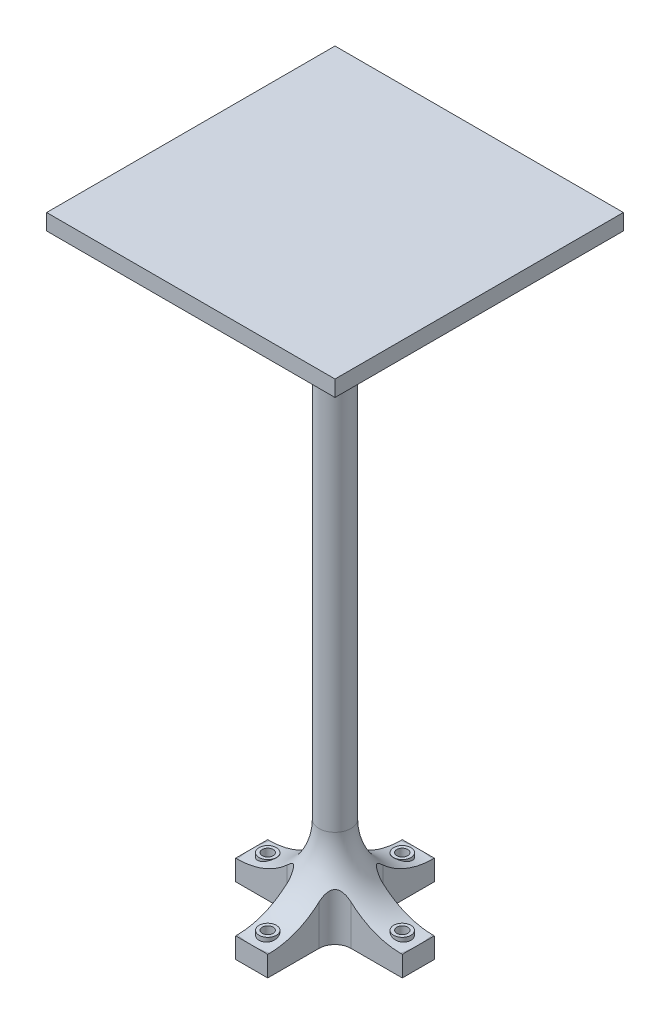
SolidWorks part; units mm, degrees
ref_plane "Front Plane" through (0, 0, 0) normal (0, 0, 1) x (1, 0, 0)
ref_plane "Top Plane" through (0, 0, 0) normal (0, 1, 0) x (1, 0, 0)
ref_plane "Right Plane" through (0, 0, 0) normal (1, 0, 0) x (0, 0, -1)
sketch "Sketch1" plane through (0, 0, 0) normal (0, 1, 0) x (1, 0, 0)
  line L1 (4.3301, 7.5) -> (-4.3301, 7.5)
  line L2 (-4.3301, 7.5) -> (-8.6603, 0)
  line L3 (-8.6603, 0) -> (-4.3301, -7.5)
  line L4 (-4.3301, -7.5) -> (4.3301, -7.5)
  line L5 (4.3301, -7.5) -> (8.6603, 0)
  line L6 (8.6603, 0) -> (4.3301, 7.5)
  circle A0 centre (0, 0) radius 7.5 construction
  dimension "D1" = 15
extrude "Boss-Extrude1" [suppressed] add sketch "Sketch1" along normal mid plane 200
hole_wizard "M3 Clearance Hole1" [suppressed] positions "Sketch4" profile "Sketch5" hole size "M3" standard "ANSI Metric"
sketch "Sketch4" [suppressed] plane through (0, 0, 7.5) normal (0, 0, 1) x (1, 0, 0)
  line L0 (-4.3301, -100) -> (4.3301, -100) construction
  point P3 (0, -97)
  point P7 (0, -100)
  dimension "D1" = 3
sketch "Sketch5" plane through (0, -97, 7.5) normal (1, 0, 0) x (0, -1, 0)
  line L0 (0, 0) -> (0, 15)
  line L1 (0, 15) -> (1.7, 15)
  line L2 (1.7, 15) -> (1.7, 0)
  line L5 (1.7, 0) -> (0, 0)
  line L11 (0, -6.35) -> (0, 107.95) construction
  dimension "Thru Hole Dia." = 3.4
  dimension "Thru Hole Depth" = 15
fillet "Fillet1" [suppressed] radius 2.5
sketch "Sketch6" [suppressed] plane through (0, 100, 0) normal (0, 1, 0) x (1, 0, 0)
  line L1 (8.2735, 45) -> (-81.7265, 45)
  line L2 (8.2735, 45) -> (8.2735, -45)
  line L3 (8.2735, -45) -> (-81.7265, -45)
  line L4 (-81.7265, 45) -> (-81.7265, -45)
  arc A1 (7.9386, -1.25) -> (7.9386, 1.25) centre (5.7735, 0) ccw construction
  point P13 (8.2735, 0)
  point P14 (8.2735, 0)
  dimension "D1" = 90
extrude "Boss-Extrude2" [suppressed] add sketch "Sketch6" against normal blind 5
fillet "Fillet2" [suppressed] radius 5
sketch "Sketch8" plane through (0, 0, 0) normal (0, 1, 0) x (1, 0, 0)
  line L0 (16, 5) -> (26, 5)
  line L1 (-5, 16) -> (5, 16)
  line L2 (-5, 16) -> (-5, 26)
  line L3 (-5, 26) -> (5, 26)
  line L4 (5, 16) -> (5, 26)
  line L5 (-5, 16) -> (5, 26) construction
  line L6 (-5, 26) -> (5, 16) construction
  line L7 (16, 5) -> (16, -5)
  line L8 (16, -5) -> (26, -5)
  line L9 (26, 5) -> (26, -5)
  line L10 (5, -16) -> (5, -26)
  line L11 (5, -16) -> (-5, -16)
  line L12 (-5, -16) -> (-5, -26)
  line L13 (5, -26) -> (-5, -26)
  line L14 (-16, -5) -> (-26, -5)
  line L15 (-16, -5) -> (-16, 5)
  line L16 (-16, 5) -> (-26, 5)
  line L17 (-26, -5) -> (-26, 5)
  line L18 (-16, 5) -> (0, 5)
  line L19 (-16, -5) -> (0, -5)
  line L20 (5, 16) -> (5, 0)
  line L21 (-5, 16) -> (-5, 0)
  line L22 (16, -5) -> (0, -5)
  line L23 (16, 5) -> (0, 5)
  line L24 (-5, -16) -> (-5, 0)
  line L25 (5, -16) -> (5, 0)
  point P0 (0, 21)
  point P21 (0, 0)
  point P38 (0, 0)
  dimension "D1" = 21
  dimension "D2" = 10
  dimension "D3" = 4
  dimension "D4" = 4
extrude "Boss-Extrude4" add sketch "Sketch8" along normal blind 6.4 separate body
sketch "Sketch7" plane through (0, 6.4, 0) normal (0, 1, 0) x (1, 0, 0)
  circle A0 centre (0, 0) radius 5
  dimension "D1" = 10
extrude "Boss-Extrude3" add sketch "Sketch7" along normal blind 180
hole_wizard "M3 Clearance Hole2" positions "Sketch9" profile "Sketch10" hole size "M3" standard "ANSI Metric" end condition up to next
sketch "Sketch9" plane through (0, 6.4, 0) normal (0, 1, 0) x (1, 0, 0)
  line L2 (-26, -5) -> (-26, 5) construction
  circle A2 centre (0, 0) radius 5
  circle A3 centre (0, 0) radius 5
  point P11 (-21, 0)
  point P15 (-26, 0)
  point P20 (0, 21)
  point P21 (21, 0)
  point P22 (0, -21)
  point P23 (0, 0)
  dimension "D1" = 5
  dimension "D3" = 0
  dimension "D2" = 4
sketch "Sketch10" plane through (-21, 6.4, 0) normal (1, 0, 0) x (0, 0, 1)
  line L0 (0, 0) -> (0, 6.4)
  line L1 (0, 6.4) -> (1.7, 6.4)
  line L2 (1.7, 6.4) -> (1.7, 0)
  line L5 (1.7, 0) -> (0, 0)
  line L11 (0, -6.35) -> (0, 107.95) construction
  dimension "Thru Hole Dia." = 3.4
  dimension "Thru Hole Depth" = 6.4
sketch "Sketch11" plane through (0, 186.4, 0) normal (0, 1, 0) x (1, 0, 0)
  line L1 (-45, 45) -> (45, 45)
  line L2 (-45, 45) -> (-45, -45)
  line L3 (-45, -45) -> (45, -45)
  line L4 (45, 45) -> (45, -45)
  line L5 (-45, 45) -> (45, -45) construction
  line L6 (-45, -45) -> (45, 45) construction
  point P0 (0, 0)
  dimension "D1" = 90
extrude "Boss-Extrude5" add sketch "Sketch11" along normal blind 5
fillet "Fillet3" radius 5 4 edges at (5, 3.2, -5) (5, 3.2, 5) (-5, 3.2, 5) (-5, 3.2, -5)
fillet "Fillet4" radius 21 1 edges at (0, 6.4, 5)
fillet "Fillet5" radius 10 1 edges at (0, 186.4, 5)
sketch "Sketch12" plane through (0, 0, 0) normal (0, -1, 0) x (1, 0, 0)
  circle A0 centre (0, -21) radius 1.7 construction
  circle A1 centre (0, -21) radius 1.7
  circle A2 centre (0, -21) radius 2.7
  circle A3 centre (-21, 0) radius 2.7
  circle A4 centre (-21, 0) radius 1.7
  circle A5 centre (0, 21) radius 2.7
  circle A6 centre (0, 21) radius 1.7
  circle A7 centre (21, 0) radius 2.7
  circle A8 centre (21, 0) radius 1.7
  point P5 (-23.4201, -2.2902)
  point P6 (0, 0)
  point P20 (0, 0)
  dimension "D1" = 1
  dimension "D2" = 4
extrude "Boss-Extrude6" add sketch "Sketch12" against normal blind 7.9
